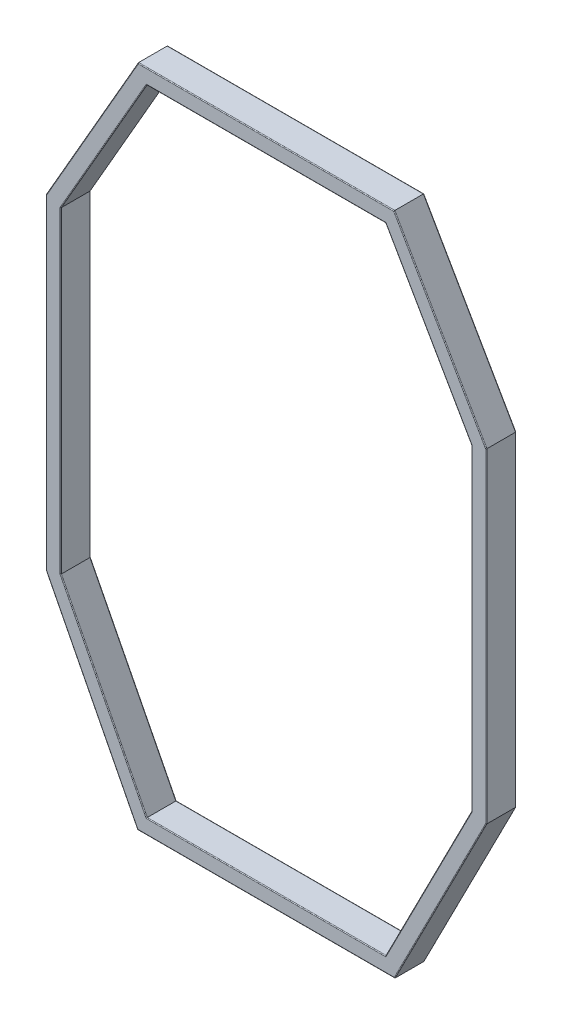
SolidWorks part; units mm, degrees
ref_plane "Plan de face" through (0, 0, 0) normal (0, 0, 1) x (1, 0, 0)
ref_plane "Plan de dessus" through (0, 0, 0) normal (0, 1, 0) x (1, 0, 0)
ref_plane "Plan de droite" through (0, 0, 0) normal (1, 0, 0) x (0, 0, -1)
sketch "Esquisse1" plane through (0, 0, 0) normal (0, 0, 1) x (1, 0, 0)
  line L0 (0, 0) -> (0, 1700) construction
  line L1 (-320, 1700) -> (320, 1700)
  line L2 (320, 1700) -> (550, 1300)
  line L3 (550, 1300) -> (550, 450)
  line L4 (550, 450) -> (320, 0)
  line L5 (320, 0) -> (-320, 0)
  line L6 (250, 1700) -> (250, 0) construction
  line L7 (320, 0) -> (320, 1700) construction
  line L8 (550, 1300) -> (0, 1300) construction
  line L9 (-320, 1700) -> (-550, 1300)
  line L10 (-550, 1300) -> (-550, 450)
  line L11 (-550, 450) -> (-320, 0)
  line L12 (-590, 1310.6802) -> (-590, 440.3702)
  line L13 (-590, 440.3702) -> (-344.4774, -40)
  line L14 (344.4774, -40) -> (-344.4774, -40)
  line L15 (590, 440.3702) -> (344.4774, -40)
  line L16 (590, 1310.6802) -> (590, 440.3702)
  line L17 (343.1411, 1740) -> (590, 1310.6802)
  line L18 (-343.1411, 1740) -> (343.1411, 1740)
  line L19 (-343.1411, 1740) -> (-590, 1310.6802)
  dimension "D1" = 250
  dimension "D2" = 300
  dimension "D3" = 70
  dimension "D4" = 1700
  dimension "D5" = 450
  dimension "D6" = 1300
  dimension "D7" = 40
extrude "Boss.-Extru.1" add sketch "Esquisse1" along normal blind 80
shell "Coque1" thickness 4
fillet "Congé1" radius 2 64 edges at (-438.1571, 1502.534, 76) (0, 1704, 76) (438.1571, 1502.534, 76) (554, 875.0525, 76) (438.2239, 222.5185, 76) (0, -4, 76) (-438.2239, 222.5185, 76) (-554, 875.0525, 76) (-586, 875.4727, 76) (-464.0148, 202.6666, 76) (0, -36, 76) (464.0148, 202.6666, 76) (586, 875.4727, 76) (463.4135, 1522.8061, 76) (0, 1736, 76) (-463.4135, 1522.8061, 76) (0, 1700, 0) (435, 1500, 0) (550, 875, 0) (435, 225, 0) (0, 0, 0) (-435, 225, 0) (-550, 875, 0) (-435, 1500, 0) (-590, 875.5252, 0) (-467.2387, 200.1851, 0) (0, -40, 0) (467.2387, 200.1851, 0) (590, 875.5252, 0) (466.5705, 1525.3401, 0) (0, 1740, 0) (-466.5705, 1525.3401, 0) (-554, 875.0525, 4) (-438.2239, 222.5185, 4) (0, -4, 4) (438.2239, 222.5185, 4) (554, 875.0525, 4) (438.1571, 1502.534, 4) (0, 1704, 4) (-438.1571, 1502.534, 4) (0, 1736, 4) (463.4135, 1522.8061, 4) (586, 875.4727, 4) (464.0148, 202.6666, 4) (0, -36, 4) (-464.0148, 202.6666, 4) (-586, 875.4727, 4) (-463.4135, 1522.8061, 4) (-435, 225, 80) (0, 0, 80) (435, 225, 80) (550, 875, 80) (435, 1500, 80) (0, 1700, 80) (-435, 1500, 80) (-550, 875, 80) (0, 1740, 80) (466.5705, 1525.3401, 80) (590, 875.5252, 80) (467.2387, 200.1851, 80) (0, -40, 80) (-467.2387, 200.1851, 80) (-590, 875.5252, 80) (-466.5705, 1525.3401, 80)
